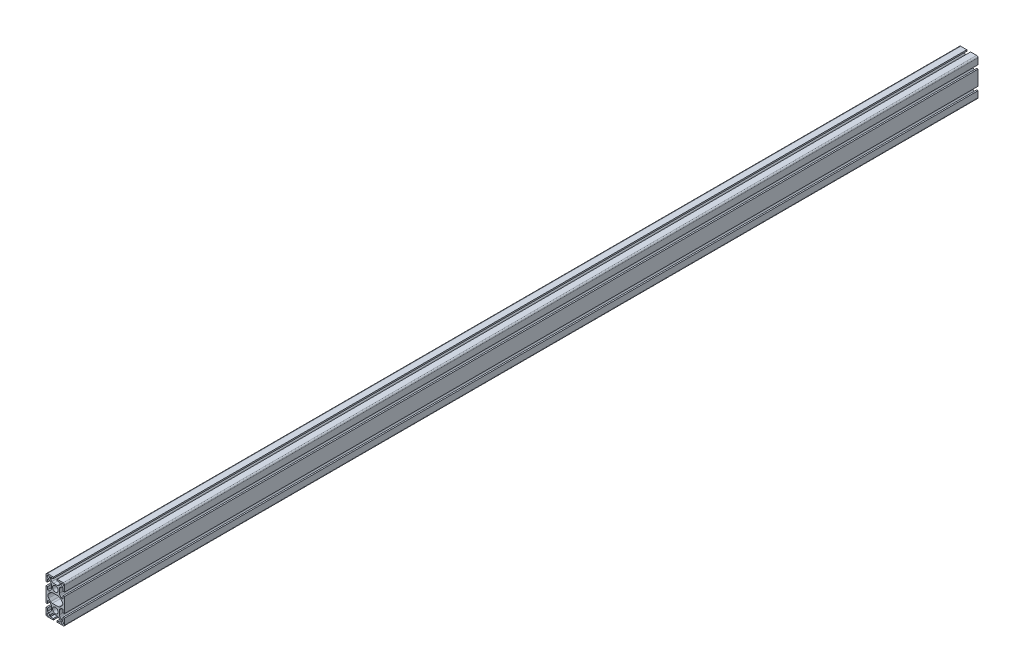
SolidWorks part; units mm, degrees
ref_plane "Front Plane" through (0, 0, 0) normal (0, 0, 1) x (1, 0, 0)
ref_plane "Top Plane" through (0, 0, 0) normal (0, 1, 0) x (1, 0, 0)
ref_plane "Right Plane" through (0, 0, 0) normal (1, 0, 0) x (0, 0, -1)
sketch "Sketch1" plane through (0, 0, 0) normal (0, 0, 1) x (1, 0, 0)
  line L0 (-17, -40) -> (-4.1, -40)
  line L1 (-4.1, -40) -> (-4.1, -37)
  line L2 (-4.1, -37) -> (-10.5, -37)
  line L3 (-10.5, -37) -> (-10.5, -33.6627)
  line L4 (-10.0314, -32.5314) -> (-7.4645, -29.9645)
  line L5 (-3.9289, -28.5) -> (3.9289, -28.5)
  line L6 (7.4645, -29.9645) -> (10.0314, -32.5314)
  line L7 (10.5, -33.6627) -> (10.5, -37)
  line L8 (10.5, -37) -> (4.1, -37)
  line L9 (4.1, -37) -> (4.1, -40)
  line L10 (4.1, -40) -> (17, -40)
  line L11 (20, -37) -> (20, -24.1)
  line L12 (20, -24.1) -> (17, -24.1)
  line L13 (17, -24.1) -> (17, -30.5)
  line L14 (17, -30.5) -> (13.6627, -30.5)
  line L15 (12.5314, -30.0314) -> (9.9645, -27.4645)
  line L16 (8.5, -23.9289) -> (8.5, -16.0711)
  line L17 (9.9645, -12.5355) -> (12.5314, -9.9686)
  line L18 (13.6627, -9.5) -> (17, -9.5)
  line L19 (17, -9.5) -> (17, -15.9)
  line L20 (17, -15.9) -> (20, -15.9)
  line L21 (20, -15.9) -> (20, 15.9)
  line L22 (20, 15.9) -> (17, 15.9)
  line L23 (17, 15.9) -> (17, 9.5)
  line L24 (17, 9.5) -> (13.6627, 9.5)
  line L25 (12.5314, 9.9686) -> (9.9645, 12.5355)
  line L26 (8.5, 16.0711) -> (8.5, 23.9289)
  line L27 (9.9645, 27.4645) -> (12.5314, 30.0314)
  line L28 (13.6627, 30.5) -> (17, 30.5)
  line L29 (17, 30.5) -> (17, 24.1)
  line L30 (17, 24.1) -> (20, 24.1)
  line L31 (20, 24.1) -> (20, 37)
  line L32 (17, 40) -> (4.1, 40)
  line L33 (4.1, 40) -> (4.1, 37)
  line L34 (4.1, 37) -> (10.5, 37)
  line L35 (10.5, 37) -> (10.5, 33.6627)
  line L36 (10.0314, 32.5314) -> (7.4645, 29.9645)
  line L37 (3.9289, 28.5) -> (-3.9289, 28.5)
  line L38 (-7.4645, 29.9645) -> (-10.0314, 32.5314)
  line L39 (-10.5, 33.6627) -> (-10.5, 37)
  line L40 (-10.5, 37) -> (-4.1, 37)
  line L41 (-4.1, 37) -> (-4.1, 40)
  line L42 (-4.1, 40) -> (-17, 40)
  line L43 (-20, 37) -> (-20, 24.1)
  line L44 (-20, 24.1) -> (-17, 24.1)
  line L45 (-17, 24.1) -> (-17, 30.5)
  line L46 (-17, 30.5) -> (-13.6627, 30.5)
  line L47 (-12.5314, 30.0314) -> (-9.9645, 27.4645)
  line L48 (-8.5, 23.9289) -> (-8.5, 16.0711)
  line L49 (-9.9645, 12.5355) -> (-12.5314, 9.9686)
  line L50 (-13.6627, 9.5) -> (-17, 9.5)
  line L51 (-17, 9.5) -> (-17, 15.9)
  line L52 (-17, 15.9) -> (-20, 15.9)
  line L53 (-20, 15.9) -> (-20, -15.9)
  line L54 (-20, -15.9) -> (-17, -15.9)
  line L55 (-17, -15.9) -> (-17, -9.5)
  line L56 (-17, -9.5) -> (-13.6627, -9.5)
  line L57 (-12.5314, -9.9686) -> (-9.9645, -12.5355)
  line L58 (-8.5, -16.0711) -> (-8.5, -23.9289)
  line L59 (-9.9645, -27.4645) -> (-12.5314, -30.0314)
  line L60 (-13.6627, -30.5) -> (-17, -30.5)
  line L61 (-17, -30.5) -> (-17, -24.1)
  line L62 (-17, -24.1) -> (-20, -24.1)
  line L63 (-20, -24.1) -> (-20, -37)
  line L64 (-14.2426, -4.2426) -> (-9.9497, -8.5355)
  line L65 (-6.4142, -10) -> (6.4142, -10)
  line L66 (9.9497, -8.5355) -> (14.2426, -4.2426)
  line L67 (14.2426, 4.2426) -> (9.9497, 8.5355)
  line L68 (6.4142, 10) -> (-6.4142, 10)
  line L69 (-9.9497, 8.5355) -> (-14.2426, 4.2426)
  arc A0 (-20, -37) -> (-17, -40) centre (-17, -37) ccw
  arc A1 (-10.5, -33.6627) -> (-10.0314, -32.5314) centre (-8.9, -33.6627) cw
  arc A2 (-7.4645, -29.9645) -> (-3.9289, -28.5) centre (-3.9289, -33.5) cw
  arc A3 (3.9289, -28.5) -> (7.4645, -29.9645) centre (3.9289, -33.5) cw
  arc A4 (10.0314, -32.5314) -> (10.5, -33.6627) centre (8.9, -33.6627) cw
  arc A5 (17, -40) -> (20, -37) centre (17, -37) ccw
  arc A6 (13.6627, -30.5) -> (12.5314, -30.0314) centre (13.6627, -28.9) cw
  arc A7 (9.9645, -27.4645) -> (8.5, -23.9289) centre (13.5, -23.9289) cw
  arc A8 (8.5, -16.0711) -> (9.9645, -12.5355) centre (13.5, -16.0711) cw
  arc A9 (12.5314, -9.9686) -> (13.6627, -9.5) centre (13.6627, -11.1) cw
  arc A10 (13.6627, 9.5) -> (12.5314, 9.9686) centre (13.6627, 11.1) cw
  arc A11 (9.9645, 12.5355) -> (8.5, 16.0711) centre (13.5, 16.0711) cw
  arc A12 (8.5, 23.9289) -> (9.9645, 27.4645) centre (13.5, 23.9289) cw
  arc A13 (12.5314, 30.0314) -> (13.6627, 30.5) centre (13.6627, 28.9) cw
  arc A14 (20, 37) -> (17, 40) centre (17, 37) ccw
  arc A15 (10.5, 33.6627) -> (10.0314, 32.5314) centre (8.9, 33.6627) cw
  arc A16 (7.4645, 29.9645) -> (3.9289, 28.5) centre (3.9289, 33.5) cw
  arc A17 (-3.9289, 28.5) -> (-7.4645, 29.9645) centre (-3.9289, 33.5) cw
  arc A18 (-10.0314, 32.5314) -> (-10.5, 33.6627) centre (-8.9, 33.6627) cw
  arc A19 (-17, 40) -> (-20, 37) centre (-17, 37) ccw
  arc A20 (-13.6627, 30.5) -> (-12.5314, 30.0314) centre (-13.6627, 28.9) cw
  arc A21 (-9.9645, 27.4645) -> (-8.5, 23.9289) centre (-13.5, 23.9289) cw
  arc A22 (-8.5, 16.0711) -> (-9.9645, 12.5355) centre (-13.5, 16.0711) cw
  arc A23 (-12.5314, 9.9686) -> (-13.6627, 9.5) centre (-13.6627, 11.1) cw
  arc A24 (-13.6627, -9.5) -> (-12.5314, -9.9686) centre (-13.6627, -11.1) cw
  arc A25 (-9.9645, -12.5355) -> (-8.5, -16.0711) centre (-13.5, -16.0711) cw
  arc A26 (-8.5, -23.9289) -> (-9.9645, -27.4645) centre (-13.5, -23.9289) cw
  arc A27 (-12.5314, -30.0314) -> (-13.6627, -30.5) centre (-13.6627, -28.9) cw
  circle A28 centre (15, 35) radius 2.5
  circle A29 centre (15, -35) radius 2.5
  circle A30 centre (0, 20) radius 6
  circle A31 centre (0, -20) radius 6
  arc A32 (-14.2426, 4.2426) -> (-14.2426, -4.2426) centre (-10, 0) ccw
  arc A33 (-9.9497, -8.5355) -> (-6.4142, -10) centre (-6.4142, -5) ccw
  arc A34 (6.4142, -10) -> (9.9497, -8.5355) centre (6.4142, -5) ccw
  arc A35 (14.2426, -4.2426) -> (14.2426, 4.2426) centre (10, 0) ccw
  arc A36 (9.9497, 8.5355) -> (6.4142, 10) centre (6.4142, 5) ccw
  arc A37 (-6.4142, 10) -> (-9.9497, 8.5355) centre (-6.4142, 5) ccw
  circle A38 centre (-15, 35) radius 2.5
  circle A39 centre (-15, -35) radius 2.5
  dimension "D1" = 40
  dimension "D2" = 80
extrude "Boss-Extrude1" add sketch "Sketch1" against normal blind 1961
